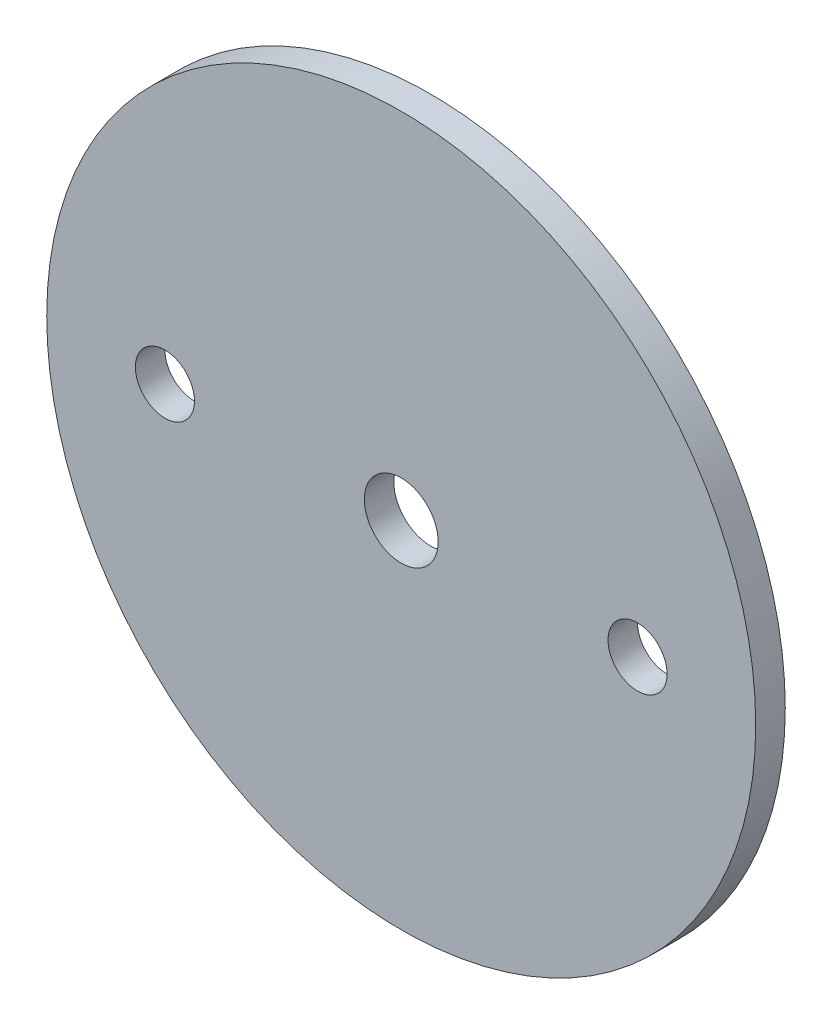
SolidWorks part; units mm, degrees
ref_plane "Front Plane" through (0, 0, 0) normal (0, 0, 1) x (1, 0, 0)
ref_plane "Top Plane" through (0, 0, 0) normal (0, 1, 0) x (1, 0, 0)
ref_plane "Right Plane" through (0, 0, 0) normal (1, 0, 0) x (0, 0, -1)
sketch "Sketch1" plane through (0, 0, 0) normal (0, 0, 1) x (1, 0, 0)
  circle A0 centre (0, 0) radius 38.1
extrude "Boss-Extrude1" add sketch "Sketch1" along normal mid plane 3.175
sketch "Sketch2" plane through (0, 0, 1.5875) normal (0, 0, 1) x (1, 0, 0)
  line L0 (-1000, 0) -> (49000, 0) construction
  line L1 (0, -1000) -> (0, 49000) construction
  point P4 (25.4, 0)
  point P5 (-25.4, 0)
  dimension "D2" = 50.8
  dimension "D1" = 25.4
hole_wizard "1/4 (0.25) Diameter Hole1" positions "Sketch2" profile "Sketch3" hole size "1/4" standard "ANSI Inch" end condition through all
sketch "Sketch3" plane through (-25.4, 0, 1.5875) normal (1, 0, 0) x (0, -1, 0)
  line L0 (0, 0) -> (0, 3.175)
  line L1 (0, 3.175) -> (3.175, 3.175)
  line L2 (3.175, 3.175) -> (3.175, 0)
  line L5 (3.175, 0) -> (0, 0)
  line L11 (0, -6.35) -> (0, 107.95) construction
  dimension "Thru Hole Dia." = 6.35
  dimension "Thru Hole Depth" = 3.175
sketch "Sketch4" plane through (0, 0, 1.5875) normal (0, 0, 1) x (1, 0, 0)
  point P0 (0, 0)
hole_wizard "5/16 (0.3125) Diameter Hole1" positions "Sketch4" profile "Sketch5" hole size "5/16" standard "ANSI Inch"
sketch "Sketch5" plane through (0, 0, 1.5875) normal (1, 0, 0) x (0, -1, 0)
  line L0 (0, 0) -> (0, 3.302)
  line L1 (0, 3.302) -> (3.9687, 3.302)
  line L2 (3.9687, 3.302) -> (3.9688, 0)
  line L5 (3.9688, 0) -> (0, 0)
  line L10 (0, 3.302) -> (-3.9688, 3.302) construction
  line L11 (0, -6.35) -> (0, 107.95) construction
  dimension "Hole Dia." = 7.9375
  dimension "Hole Depth" = 3.302
  dimension "Drill Angle" = 180
equation "\"AIRFRAME_OD\"= 3.142in"
equation "\"AIRFRAME_ID\"= 3.00in"
equation "\"FLAT_T\"= 0.125in"
equation "\"NOSE_EXP_L\"= 3.5in"
equation "\"NOSE_SHOULDER_L\"= 1.5in"
equation "\"MAIN_L\"= 30in"
equation "\"RECO_COUP_L\"= 6in"
equation "\"RECO_SWITCH_L\"= 1.5in"
equation "\"DROGUE_L\"= 14in"
equation "\"ATS_FORE_COUP_L\"= 4in"
equation "\"ATS_AFT_COUP_L\"= 2.5in"
equation "\"LOWER_L\"= 16in"
equation "\"FIN_N\"= 4"
equation "\"CR_AFT_X\"= 0.5in"
equation "\"CR_FORE_X\"= 6in"
equation "\"FIN_ROOT\"= 5in"
equation "\"FIN_X\"= 0.75in"
equation "\"MOTOR_OD\"= 2.25in"
equation "\"MOTOR_ID\"= 2.126in"
equation "\"COUPLER_OD\"= 2.998in"
equation "\"COUPLER_ID\"= 2.875in"
equation "\"D1@Sketch1\"=\"AIRFRAME_ID\""
equation "\"D1@Boss-Extrude1\"=\"FLAT_T\""
equation "\"RECO_ROD_X\"= 1.5in"
equation "\"ATS_ROD_X\"= 2in"
equation "\"D2@Sketch2\"=\"ATS_ROD_X\""
